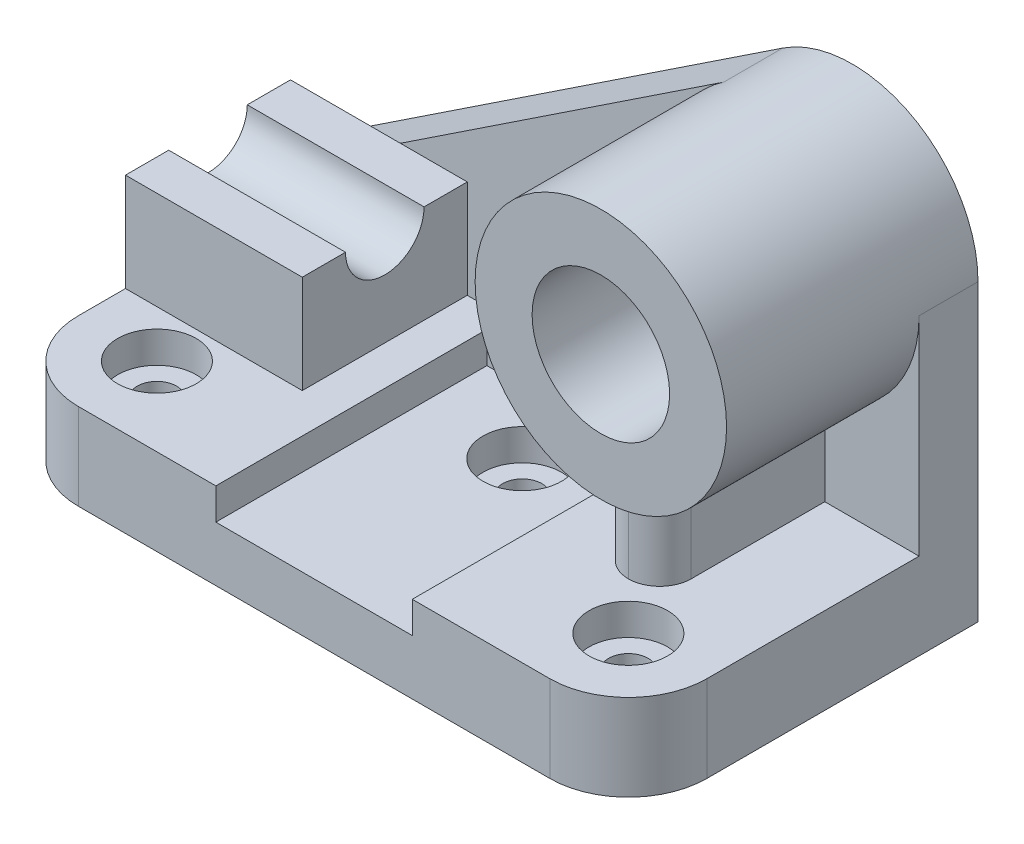
SolidWorks part; units mm, degrees
ref_plane "Alzado" through (0, 0, 0) normal (0, 0, 1) x (1, 0, 0)
ref_plane "Planta" through (0, 0, 0) normal (0, 1, 0) x (1, 0, 0)
ref_plane "Vista lateral" through (0, 0, 0) normal (1, 0, 0) x (0, 0, -1)
sketch "Croquis3" plane through (0, 0, 0) normal (0, 0, 1) x (1, 0, 0)
  line L0 (0, 0) -> (160, 0)
  line L1 (160, 0) -> (160, 22)
  line L2 (160, 22) -> (0, 22)
  line L3 (0, 22) -> (0, 0)
  dimension "D1" = 160
  dimension "D2" = 22
extrude "Saliente-Extruir1" add sketch "Croquis3" against normal blind 89
sketch "Croquis6" plane through (0, 0, 0) normal (0, 0, 1) x (1, 0, 0)
  line L0 (160, 22) -> (0, 22) construction
  line L1 (55, 22) -> (105, 22)
  line L2 (55, 22) -> (55, 14)
  line L3 (55, 14) -> (105, 14)
  line L4 (105, 22) -> (105, 14)
  dimension "D1" = 50
  dimension "D2" = 8
  dimension "D3" = 55
extrude "Cortar-Extruir1" cut sketch "Croquis6" against normal blind 69 contours L1 L4 L3 L2
fillet "Redondeo1" radius 20 1 edges at (160, 11, 0)
fillet "Redondeo2" radius 20 1 edges at (0, 11, 0)
sketch "Croquis7" plane through (0, 0, -89) normal (0, 0, -1) x (-1, 0, 0)
  line L0 (0, 22) -> (-160, 22)
  line L1 (-160, 22) -> (-160, 75)
  line L2 (0, 0) -> (0, 22) construction
  line L4 (-110.3018, 101.6603) -> (-5.3632, 31.9976)
  line L5 (-20, 0) -> (-140, 0) construction
  arc A0 (-110.3018, 101.6603) -> (-160, 75) centre (-128, 75) ccw
  arc A1 (-5.3632, 31.9976) -> (0, 22) centre (-12, 22) cw
  circle A2 centre (-128, 75) radius 17.5
  dimension "D2" = 35
  dimension "D3" = 32
  dimension "D4" = 12
  dimension "D1" = 75
sketch3d "Croquis3D2" plane through (0, 0, 0) normal (0, 0, 1) x (1, 0, 0)
extrude "Saliente-Extruir3" add sketch "Croquis7" against normal blind 15 separate body
sketch "Croquis8" plane through (0, 0, -74) normal (0, 0, 1) x (1, 0, 0)
  circle A0 centre (128, 75) radius 17.5
  circle A1 centre (128, 75) radius 32
  dimension "D1" = 35
  dimension "D2" = 64
extrude "Saliente-Extruir4" add sketch "Croquis8" along normal blind 49
sketch "Croquis9" plane through (0, 0, -74) normal (0, 0, 1) x (1, 0, 0)
  line L0 (0, 22) -> (45, 22)
  line L1 (55, 22) -> (20, 22) construction
  line L2 (45, 22) -> (45, 47)
  line L3 (45, 47) -> (0, 47)
  line L4 (0, 47) -> (0, 22)
  line L5 (128, 75) -> (128, 22) construction
  line L7 (120, 47) -> (136, 47)
  line L8 (136, 47) -> (136, 22)
  line L9 (0, 22) -> (160, 22) construction
  line L10 (136, 22) -> (120, 22)
  line L11 (140, 22) -> (105, 22) construction
  line L12 (120, 22) -> (120, 47)
  point P14 (128, 47)
  dimension "D1" = 45
  dimension "D2" = 25
  dimension "D3" = 16
  dimension "D4" = 25
extrude "Saliente-Extruir5" add sketch "Croquis9" along normal blind 42
fillet "Redondeo3" radius 8 1 edges at (136, 33.0081, -32)
fillet "Redondeo4" radius 8 1 edges at (120, 33.0081, -32)
ref_plane "Plano1" through (0, 0, -53) normal (0, 0, 1) x (1, 0, 0)
sketch "Croquis10" plane through (0, 0, -53) normal (0, 0, 1) x (1, 0, 0)
  line L0 (0, 47) -> (0, 37)
  line L1 (0, 47) -> (0, 22) construction
  line L2 (0, 37) -> (45, 37)
  line L3 (45, 22) -> (45, 47) construction
  line L4 (45, 37) -> (45, 47)
  line L5 (45, 47) -> (0, 47)
  dimension "D1" = 10
revolve "Cortar-Revolución1" cut sketch "Croquis10" angle 360 about L5
sketch "Croquis14" plane through (0, 0, -53) normal (0, 0, 1) x (1, 0, 0)
  line L0 (70, 14) -> (70, 6)
  line L1 (55, 14) -> (105, 14) construction
  line L2 (70, 6) -> (75, 6)
  line L3 (75, 6) -> (75, -24.1238)
  line L4 (75, -24.1238) -> (80, -24.1238)
  line L5 (80, -24.1238) -> (80, 14)
  line L6 (55, 14) -> (105, 14) construction
  line L7 (80, 14) -> (70, 14)
  line L8 (80, 14) -> (80, -48.4875) construction
  dimension "D1" = 5
  dimension "D2" = 10
  dimension "D3" = 8
revolve "Cortar-Revolución2" cut sketch "Croquis14" angle 360 about L8
ref_plane "Plano2" through (0, 0, -20) normal (0, 0, 1) x (1, 0, 0)
sketch "Croquis16" plane through (0, 0, -20) normal (0, 0, 1) x (1, 0, 0)
  line L0 (20, 59.3324) -> (20, 0) construction
  line L1 (0, 0) -> (20, 0) construction
  line L4 (20, 22) -> (0, 22) construction
  line L5 (0, 22) -> (45, 22) construction
  line L6 (10, 22) -> (10, 14)
  line L7 (10, 14) -> (15, 14)
  line L8 (15, 14) -> (15, -14.561)
  line L9 (15, -14.561) -> (20, -14.561)
  line L10 (20, -14.561) -> (20, 22)
  line L12 (10, 22) -> (20, 22)
  dimension "D1" = 20
  dimension "D2" = 10
  dimension "D3" = 8
  dimension "D4" = 5
revolve "Cortar-Revolución3" cut sketch "Croquis16" angle 360 about L0
sketch "Croquis17" plane through (0, 0, -20) normal (0, 0, 1) x (1, 0, 0)
  line L0 (140, -22.8568) -> (140, 38.3143) construction
  line L1 (140, 22) -> (150, 22)
  line L2 (136, 22) -> (160, 22) construction
  line L3 (160, 22) -> (140, 22) construction
  line L4 (150, 22) -> (150, 14)
  line L5 (150, 14) -> (145, 14)
  line L6 (145, 14) -> (145, 0)
  line L7 (140, 0) -> (160, 0) construction
  line L8 (145, 0) -> (140, 0)
  line L9 (140, 0) -> (140, 22)
  dimension "D1" = 20
  dimension "D2" = 8
  dimension "D3" = 5
  dimension "D4" = 10
revolve "Cortar-Revolución4" cut sketch "Croquis17" angle 360 about L0
